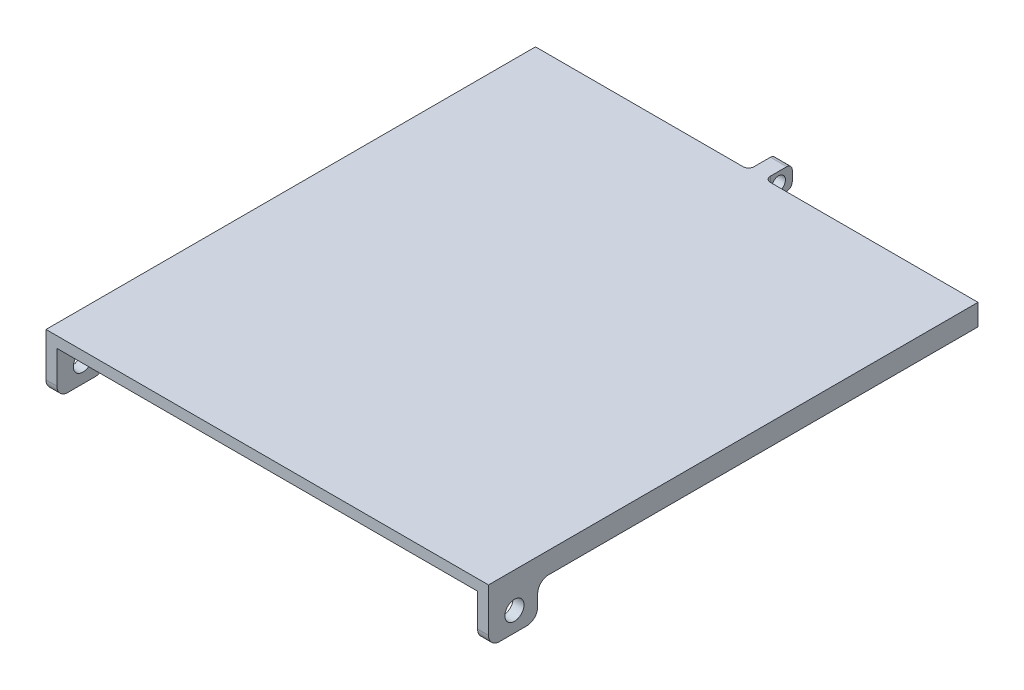
SolidWorks part; units mm, degrees
ref_plane "Front Plane" through (0, 0, 0) normal (0, 0, 1) x (1, 0, 0)
ref_plane "Top Plane" through (0, 0, 0) normal (0, 1, 0) x (1, 0, 0)
ref_plane "Right Plane" through (0, 0, 0) normal (1, 0, 0) x (0, 0, -1)
sketch "Sketch1" plane through (0, 0, 0) normal (0, 1, 0) x (1, 0, 0)
  line L0 (-46.1415, 4.4886) -> (-46.1415, 13.4886)
  line L2 (-46.1415, 13.4886) -> (-46.1415, 92.0886)
  line L3 (-46.1415, 92.0886) -> (30.8585, 92.0886)
  line L4 (30.8585, 92.0886) -> (30.8585, 13.4886)
  line L6 (30.8585, 13.4886) -> (30.8585, 4.4886)
  line L7 (30.8585, 4.4886) -> (32.8585, 4.4886)
  line L8 (32.8585, 4.4886) -> (32.8585, 94.0886)
  line L11 (32.8585, 94.0886) -> (-48.1415, 94.0886)
  line L13 (-48.1415, 94.0886) -> (-48.1415, 4.4886)
  line L14 (-48.1415, 4.4886) -> (-46.1415, 4.4886)
  dimension "D1" = 77
  dimension "D2" = 2
  dimension "D3" = 87.6
  dimension "D4" = 87.6
  dimension "D5" = 2
  dimension "D8" = 2
extrude "Boss-Extrude2" add sketch "Sketch1" along normal blind 8 contours L13 L14 L0 L2 L3 L4 L6 L7 L8 L11
sketch "Sketch2" plane through (0, 8, 0) normal (0, 1, 0) x (1, 0, 0)
  line L1 (-48.1415, 94.0886) -> (32.8585, 94.0886)
  line L2 (-48.1415, 94.0886) -> (-48.1415, 4.4886)
  line L3 (-48.1415, 4.4886) -> (32.8585, 4.4886)
  line L4 (32.8585, 94.0886) -> (32.8585, 4.4886)
  line L6 (32.8585, 4.4886) -> (32.8585, 94.0886) construction
  line L7 (30.8585, 4.4886) -> (32.8585, 4.4886) construction
  dimension "D1" = 0
  dimension "D2" = 0
extrude "Boss-Extrude3" add sketch "Sketch2" along normal blind 2
sketch "Sketch3" plane through (32.8585, 0, 0) normal (1, 0, 0) x (0, 0, -1)
  line L0 (4.4886, 10) -> (94.0886, 10) construction
  line L1 (4.4886, 10) -> (4.4886, 0) construction
  circle A0 centre (9.2386, 3.6) radius 1.75
  dimension "D1" = 3.5
  dimension "D2" = 6.4
  dimension "D3" = 4.75
extrude "Cut-Extrude1" cut sketch "Sketch3" against normal through all
sketch "Sketch4" plane through (30.8585, 0, 0) normal (-1, 0, 0) x (0, 0, 1)
  line L0 (-92.0886, 8) -> (-4.4886, 8) construction
  line L1 (-94.0886, 6.1) -> (-13.4886, 6.1)
  line L2 (-94.0886, 6.1) -> (-94.0886, 0)
  line L3 (-94.0886, 0) -> (-13.4886, 0)
  line L4 (-13.4886, 6.1) -> (-13.4886, 0)
  line L5 (-94.0886, 10) -> (-94.0886, 0) construction
  dimension "D1" = 1.9
  dimension "D2" = 0
extrude "Cut-Extrude2" cut sketch "Sketch4" against normal through all both and the other way through all
sketch "Sketch5" plane through (0, 8, 0) normal (0, -1, 0) x (1, 0, 0)
  line L0 (-46.1415, -4.4886) -> (-46.1415, -92.0886) construction
  line L1 (26.7585, -13.0053) -> (-42.0415, -13.0053)
  line L2 (26.7585, -13.0053) -> (26.7585, -11.8053)
  line L3 (26.7585, -11.8053) -> (-42.0415, -11.8053)
  line L4 (-42.0415, -13.0053) -> (-42.0415, -11.8053)
  line L5 (-42.6415, -13.5553) -> (27.3585, -13.5553) construction
  dimension "D1" = 1.2
  dimension "D2" = 68.8
  dimension "D3" = 4.1
  dimension "D4" = 0.55
extrude "Boss-Extrude4" add sketch "Sketch5" along normal blind 2
fillet "Fillet2" radius 2 7 edges at (-7.6415, 8, -11.8053) (-47.1415, 0, -4.4886) (-47.1415, 0, -13.4886) (-47.1415, 6.1, -13.4886) (31.8585, 6.1, -13.4886) (31.8585, 0, -4.4886) (31.8585, 0, -13.4886)
ref_plane "Plane1" through (-7.6415, 0, 0) normal (-1, 0, 0) x (0, 0, 1)
sketch "Sketch7" plane through (-7.6415, 0, 0) normal (-1, 0, 0) x (0, 0, 1)
  line L0 (-94.0886, 10) -> (-94.0886, 6.1) construction
  line L1 (-94.0886, 10) -> (-98.0886, 10)
  line L2 (-94.0886, 10) -> (-94.0886, 6.1)
  line L3 (-94.0886, 6.1) -> (-98.0886, 6.1)
  line L4 (-99.0886, 9) -> (-99.0886, 7.1)
  arc A0 (-99.0886, 7.1) -> (-98.0886, 6.1) centre (-98.0886, 7.1) ccw
  arc A1 (-99.0886, 9) -> (-98.0886, 10) centre (-98.0886, 9) cw
  circle A2 centre (-96.5886, 8.05) radius 1.25
  point P14 (-99.0886, 10)
  point P17 (-99.0886, 8.05)
  dimension "D2" = 1
  dimension "D3" = 2.5
  dimension "D4" = 1.95
  dimension "D5" = 2.5
  dimension "D1" = 5
extrude "Boss-Extrude5" add sketch "Sketch7" along normal blind 1.5 and the other way blind 1.5
fillet "Fillet5" radius 1 2 edges at (-6.1415, 8.05, -94.0886) (-9.1415, 8.05, -94.0886)
